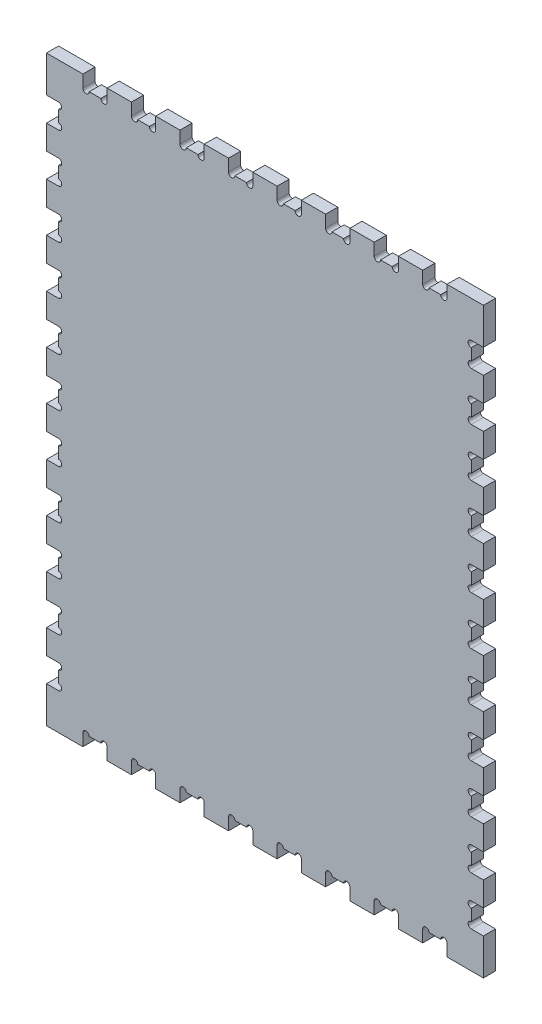
SolidWorks part; units mm, degrees
ref_plane "Front Plane" through (0, 0, 0) normal (0, 0, 1) x (1, 0, 0)
ref_plane "Top Plane" through (0, 0, 0) normal (0, 1, 0) x (1, 0, 0)
ref_plane "Right Plane" through (0, 0, 0) normal (1, 0, 0) x (0, 0, -1)
sketch "Sketch1" plane through (0, 0, 0) normal (0, 0, 1) x (1, 0, 0)
  line L1 (228.6, -304.8) -> (-228.6, -304.8)
  line L2 (228.6, -304.8) -> (228.6, 304.8)
  line L3 (228.6, 304.8) -> (-228.6, 304.8)
  line L4 (-228.6, -304.8) -> (-228.6, 304.8)
  line L5 (228.6, -304.8) -> (-228.6, 304.8) construction
  line L6 (228.6, 304.8) -> (-228.6, -304.8) construction
  line L9 (-203.2, 304.8) -> (-228.6, 304.8) construction
  point P0 (0, 0)
  dimension "D1" = 457.2
  dimension "D2" = 609.6
extrude "Boss-Extrude1" add sketch "Sketch1" along normal blind 12.7
sketch "Sketch2" plane through (0, 0, 12.7) normal (0, 0, 1) x (1, 0, 0)
  line L0 (228.6, 304.8) -> (-228.6, 304.8) construction
  line L1 (-190.5, 292.1) -> (-228.6, 292.1) construction
  line L2 (-190.5, 304.8) -> (-165.1, 304.8)
  line L3 (-190.5, 304.8) -> (-190.5, 292.1)
  line L4 (-190.5, 292.1) -> (-165.1, 292.1)
  line L5 (-165.1, 304.8) -> (-165.1, 292.1)
  line L6 (-228.6, 304.8) -> (-228.6, -304.8) construction
  circle A0 centre (-187.198, 292.1) radius 3.302
  circle A1 centre (-168.402, 292.1) radius 3.302
  line M10 (228.6, 304.8) -> (-228.6, 304.8)
  dimension "D4" = 6.604
  dimension "D5" = 6.604
  dimension "D1" = 25.4
  dimension "D2" = 12.7
  dimension "D3" = 38.1
extrude "Cut-Extrude1" cut sketch "Sketch2" against normal through all contours A1 L5 L3 A0 L4 M10 | L4 A0 | L4 A0 | L4 A1 | L4 A1 region at (-177.8, 299.0379, 12.7) region at (-187.198, 293.5014, 12.7) region at (-187.198, 290.6986, 12.7) region at (-168.402, 290.6986, 12.7) region at (-168.402, 293.5014, 12.7)
pattern_linear "LPattern1" count 8 spacing 50.8 along (1, 0, 0) of "Cut-Extrude1"
sketch "Sketch3" plane through (0, 0, 12.7) normal (0, 0, 1) x (1, 0, 0)
  line L0 (-228.6, 304.8) -> (-228.6, -304.8) construction
  line L1 (-228.6, 266.7) -> (-215.9, 266.7)
  line L2 (-228.6, 266.7) -> (-228.6, 241.3)
  line L3 (-228.6, 241.3) -> (-215.9, 241.3)
  line L4 (-215.9, 266.7) -> (-215.9, 241.3)
  line L5 (-215.9, 266.7) -> (-215.9, 304.8) construction
  line L7 (-190.5, 304.8) -> (-228.6, 304.8) construction
  circle A0 centre (-215.9, 263.398) radius 3.302
  circle A1 centre (-215.9, 244.602) radius 3.302
  dimension "D3" = 6.604
  dimension "D4" = 6.604
  dimension "D1" = 25.4
  dimension "D2" = 12.7
  dimension "D5" = 38.1
extrude "Cut-Extrude2" cut sketch "Sketch3" against normal through all contours A1 L4 A0 L1 L2 L3 | L4 A0 | L4 A1 | L4 A1 | L4 A0 region at (-222.8379, 254, 12.7) region at (-214.4986, 263.398, 12.7) region at (-217.3014, 263.398, 12.7) region at (-217.3014, 244.602, 12.7) region at (-214.4986, 244.602, 12.7)
pattern_linear "LPattern2" count 11 spacing 50.8 along (0, -1, 0) of "Cut-Extrude2"
ref_plane "Plane1" through (0, 0, 0) normal (1, 0, 0) x (0, 0, -1)
ref_plane "Plane2" through (0, 0, 0) normal (0, 1, 0) x (1, 0, 0)
mirror "Mirror1" about plane through (0, 0, 0) normal (1, 0, 0) of "LPattern2"
mirror "Mirror2" about plane through (0, 0, 0) normal (0, 1, 0) of "LPattern1"
